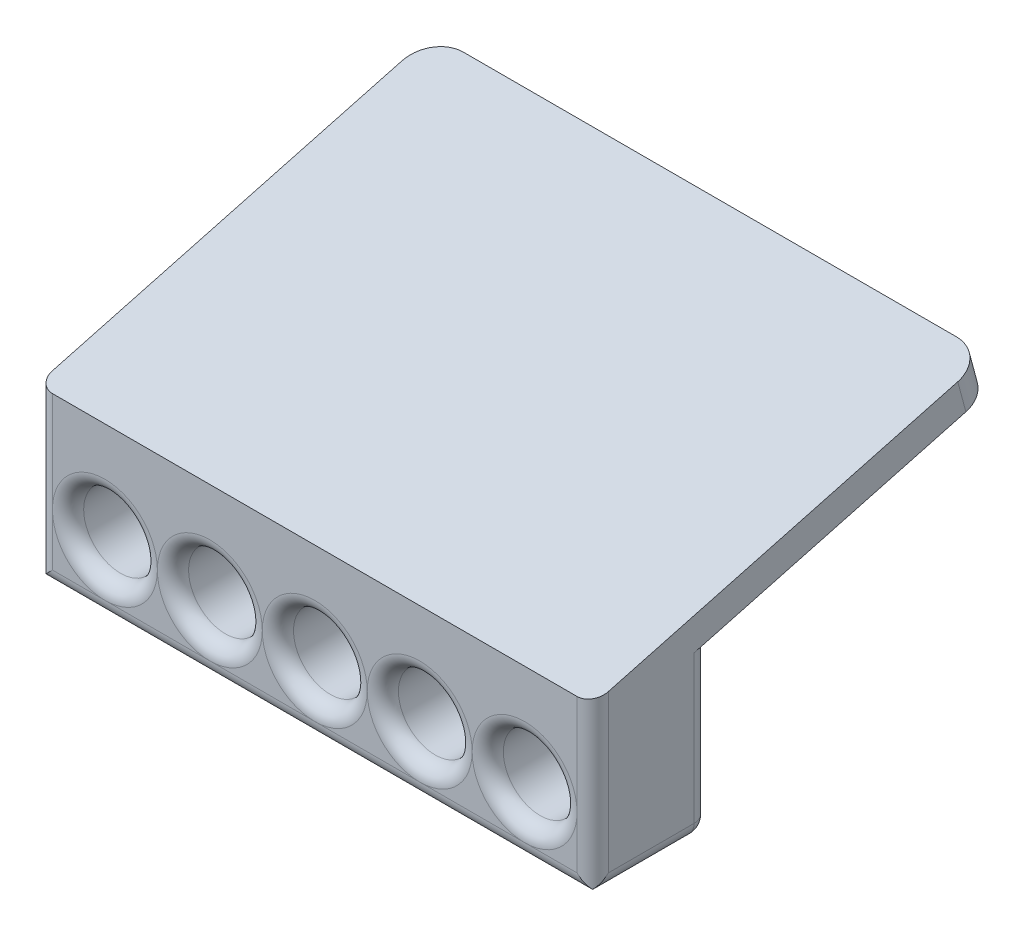
SolidWorks part; units mm, degrees
ref_plane "Front Plane" through (0, 0, 0) normal (0, 0, 1) x (1, 0, 0)
ref_plane "Top Plane" through (0, 0, 0) normal (0, 1, 0) x (1, 0, 0)
ref_plane "Right Plane" through (0, 0, 0) normal (1, 0, 0) x (0, 0, -1)
sketch "Sketch1" plane through (0, 0, 0) normal (0, 0, 1) x (1, 0, 0)
  line L1 (39.6999, -5.54) -> (-5.54, -5.54)
  line L2 (39.6999, -5.54) -> (39.6999, 5.54)
  line L3 (39.6999, 5.54) -> (-5.54, 5.54)
  line L4 (-5.54, -5.54) -> (-5.54, 5.54)
  line L5 (39.6999, -5.54) -> (-5.54, 5.54) construction
  line L6 (39.6999, 5.54) -> (-5.54, -5.54) construction
  line L7 (-3, 0) -> (-5.54, 0) construction
  line L8 (0, -3) -> (0, -5.54) construction
  circle A0 centre (0, 0) radius 3
  circle A1 centre (8.54, 0) radius 3
  circle A2 centre (17.08, 0) radius 3
  circle A3 centre (25.62, 0) radius 3
  circle A4 centre (34.16, 0) radius 3
  point P4 (17.08, 0)
  point P14 (0, 0)
  dimension "D1" = 6
  dimension "D3" = 2.54
  dimension "D4" = 2.54
  dimension "D2" = 5
extrude "Boss-Extrude1" add sketch "Sketch1" along normal blind 9.525
sketch "Sketch2" plane through (39.6999, 0, 0) normal (1, 0, 0) x (0, 0, -1)
  line L0 (-9.525, 5.54) -> (0, 8.0922)
  line L1 (0, 8.0922) -> (0, 5.54)
  line L2 (0, 5.54) -> (-9.525, 5.54)
  dimension "D1" = 15
extrude "Boss-Extrude2" add sketch "Sketch2" against normal up to surface (45.2399 mm away) up to face at (-5.54, 0, 4.7625)
fillet "Fillet1" radius 1.27 2 edges at (-5.54, -5.54, 4.7625) (39.6999, -5.54, 4.7625)
fillet "Fillet2" radius 1.27 4 edges at (-5.54, 1.9111, 0) (39.6999, 1.9111, 0) (17.08, -5.54, 0) (17.08, -5.54, 9.525)
fillet "Fillet3" radius 1.27 2 edges at (39.6999, 0.635, 9.525) (-5.54, 0.635, 9.525)
fillet "Fillet4" radius 1.27 10 edges at (28.62, 0, 9.525) (20.08, 0, 9.525) (11.54, 0, 9.525) (3, 0, 9.525) (28.62, 0, 0) (20.08, 0, 0) (11.54, 0, 0) (3, 0, 0) (37.1599, 0, 9.525) (37.1599, 0, 0)
sketch "Sketch3" plane through (0, 7.5501, 2.0231) normal (0, 0.9659, 0.2588) x (1, 0, 0)
  line L0 (-5.54, 0.7796) -> (-5.54, 26.2195)
  line L1 (-5.54, 26.2195) -> (39.6999, 26.2195)
  line L2 (39.6999, 26.2195) -> (39.6999, 0.7796)
  line L4 (-4.27, -7.7666) -> (38.4299, -7.7666)
  line L5 (39.6999, -6.4518) -> (39.6999, 0.7796)
  line L6 (38.4299, 2.0944) -> (-4.27, 2.0944)
  line L7 (-5.54, 0.7796) -> (-5.54, -6.4518)
  line L8 (-5.54, -7.7666) -> (39.6999, -7.7666)
  line L9 (39.6999, -7.7666) -> (39.6999, 0.7796)
  line L11 (-5.54, 0.7796) -> (-5.54, -7.7666)
  ellipse E4 centre (38.4299, -6.4518) end of major axis (38.4299, -7.7666) minor radius 1.27 (38.4299, -7.7666) -> (39.6999, -6.4518) ccw
  ellipse E5 centre (38.4299, 0.7796) end of major axis (38.4299, 2.0944) minor radius 1.27 (39.6999, 0.7796) -> (38.4299, 2.0944) ccw
  ellipse E6 centre (-4.27, 0.7796) end of major axis (-4.27, -0.5352) minor radius 1.27 (-4.27, 2.0944) -> (-5.54, 0.7796) ccw
  ellipse E7 centre (-4.27, -6.4518) end of major axis (-4.27, -5.137) minor radius 1.27 (-5.54, -6.4518) -> (-4.27, -7.7666) ccw
  dimension "D1" = 0
extrude "Boss-Extrude3" add sketch "Sketch3" along normal blind 2.54
sketch "Sketch4" plane through (0, -5.54, 0) normal (0, -1, 0) x (1, 0, 0)
  line L0 (-4.27, 9.525) -> (38.4299, 9.525)
  line L1 (-5.54, 8.255) -> (-5.54, 24.0428)
  line L2 (-5.54, 24.0428) -> (39.6999, 24.0428)
  line L3 (39.6999, 24.0428) -> (39.6999, 8.255)
  arc A0 (-5.168, 9.153) -> (-5.54, 8.255) centre (-4.27, 8.255) ccw construction
  arc A1 (-5.168, 9.153) -> (-5.54, 8.255) centre (-4.27, 8.255) ccw
  arc A2 (-4.27, 9.525) -> (-5.168, 9.153) centre (-4.27, 8.255) ccw construction
  arc A3 (39.328, 9.153) -> (38.4299, 9.525) centre (38.4299, 8.255) ccw construction
  arc A5 (39.6999, 8.255) -> (39.328, 9.153) centre (38.4299, 8.255) ccw construction
  arc A11 (39.6999, 8.255) -> (39.328, 9.153) centre (38.4299, 8.255) ccw
  arc A12 (39.328, 9.153) -> (38.4299, 9.525) centre (38.4299, 8.255) ccw
  arc A13 (-4.27, 9.525) -> (-5.168, 9.153) centre (-4.27, 8.255) ccw
extrude "Cut-Extrude1" cut sketch "Sketch4" against normal through all both and the other way through all
fillet "Fillet5" radius 2.54 2 edges at (39.6999, 15.563, -22.9743) (-5.54, 15.563, -22.9743)
